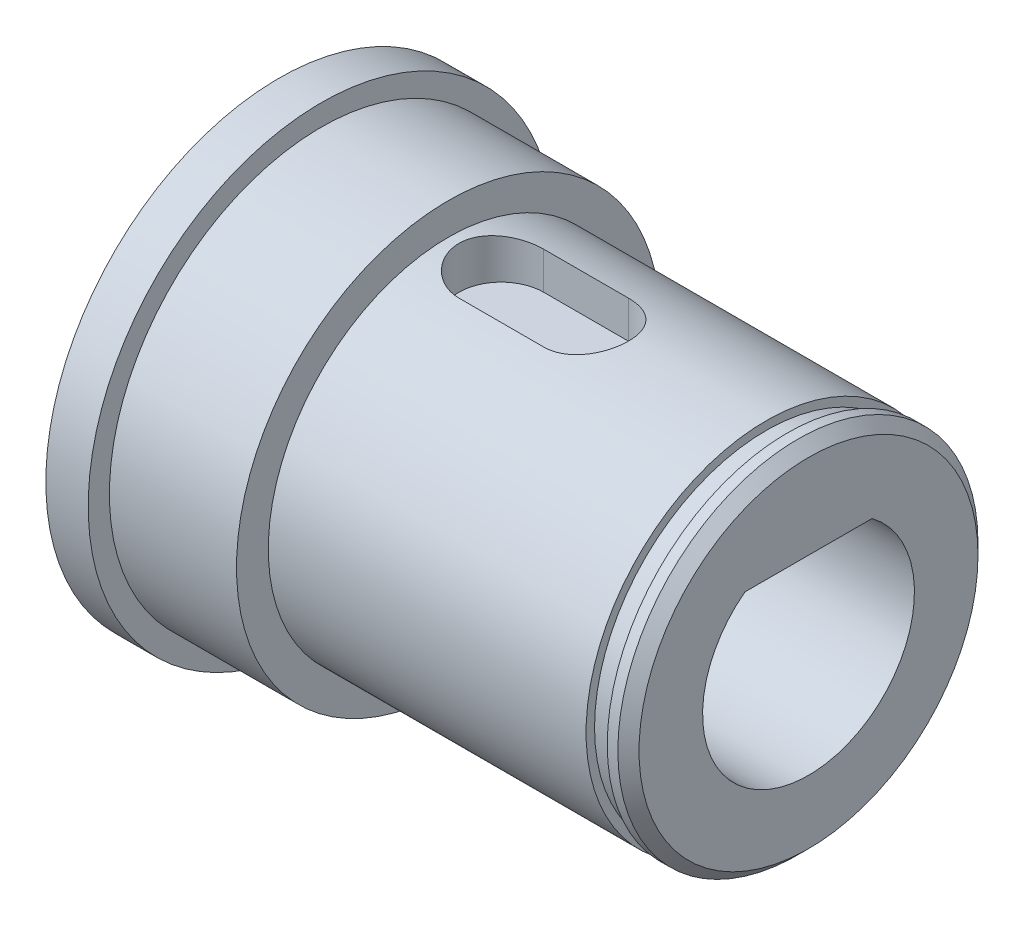
SolidWorks part; units mm, degrees
material "合金钢"
ref_plane "前视基准面" through (0, 0, 0) normal (0, 0, 1) x (1, 0, 0)
ref_plane "上视基准面" through (0, 0, 0) normal (0, 1, 0) x (1, 0, 0)
ref_plane "右视基准面" through (0, 0, 0) normal (1, 0, 0) x (0, 0, -1)
ref_axis "基准轴1" through (88.99, 0, 0) along (-1, 0, 0)
sketch "草图1" plane through (0, 0, 0) normal (1, 0, 0) x (0, 0, -1)
  circle A0 centre (0, 0) radius 11
extrude "凸台-拉伸1" add sketch "草图1" along normal blind 2
sketch "草图2" plane through (2, 0, 0) normal (1, 0, 0) x (0, 0, -1)
  circle A0 centre (0, 0) radius 10
extrude "凸台-拉伸2" add sketch "草图2" along normal blind 6
sketch "草图3" plane through (8, 0, 0) normal (1, 0, 0) x (0, 0, -1)
  circle A0 centre (0, 0) radius 8.5
extrude "凸台-拉伸3" add sketch "草图3" along normal blind 17
ref_plane "基准面1" through (0, 8.5, 0) normal (0, 1, 0) x (1, 0, 0)
sketch "草图4" plane through (0, 8.5, 0) normal (0, 1, 0) x (1, 0, 0)
  line L0 (10.5, 2) -> (14.5, 2)
  line L1 (10.5, -2) -> (14.5, -2)
  line L2 (8, -8.5) -> (8, 8.5) construction
  arc A0 (10.5, 2) -> (10.5, -2) centre (10.5, 0) ccw
  arc A1 (14.5, 2) -> (14.5, -2) centre (14.5, 0) cw
  dimension "D1" = 2
  dimension "D2" = 4
  dimension "D3" = 2.5
extrude "切除-拉伸1" cut sketch "草图4" against normal blind 2
sketch "草图5" plane through (25, 0, 0) normal (1, 0, 0) x (0, 0, -1)
  line L0 (-3, 4) -> (3, 4)
  arc A0 (-3, 4) -> (3, 4) centre (0, 0) ccw
  dimension "D1" = 10
  dimension "D2" = 4
extrude "切除-拉伸2" cut sketch "草图5" against normal through all
sketch "草图6" plane through (0, 0, 0) normal (0, 0, 1) x (1, 0, 0)
  line L1 (25, 8.5) -> (16.5, 8.5) construction
  line L2 (23, 8.1) -> (24, 8.1)
  line L3 (23, 8.1) -> (23, 8.9)
  line L4 (23, 8.9) -> (24, 8.9)
  line L5 (24, 8.1) -> (24, 8.9)
  line L6 (23, 8.1) -> (24, 8.9) construction
  line L7 (23, 8.9) -> (24, 8.1) construction
  line L8 (0, 0) -> (25, 0) construction
  line L9 (25, -8.5) -> (25, 8.5) construction
  line L10 (8, -10) -> (8, 10) construction
  point P2 (23.5, 8.5)
  dimension "D1" = 15
  dimension "D2" = 1
  dimension "D3" = 0.8
revolve "切除-旋转1" cut sketch "草图6" angle 360 about L8
chamfer "倒角1" distance 0.5 angle 45 1 edges at (25, 0, -8.5)
sketch "草图7" plane through (0, 4, 0) normal (0, -1, 0) x (1, 0, 0)
  line L1 (0, 0) -> (25, 0) construction
  line L2 (25, -8) -> (25, 8) construction
  circle A0 centre (12, 0) radius 1.5
  dimension "D1" = 3
  dimension "D2" = 13
sketch "草图8" plane through (0, 0, 0) normal (-1, 0, 0) x (0, 0, 1)
  circle A0 centre (0, 0) radius 7.5
  dimension "D1" = 15
extrude "切除-拉伸4" cut sketch "草图8" against normal blind 5
